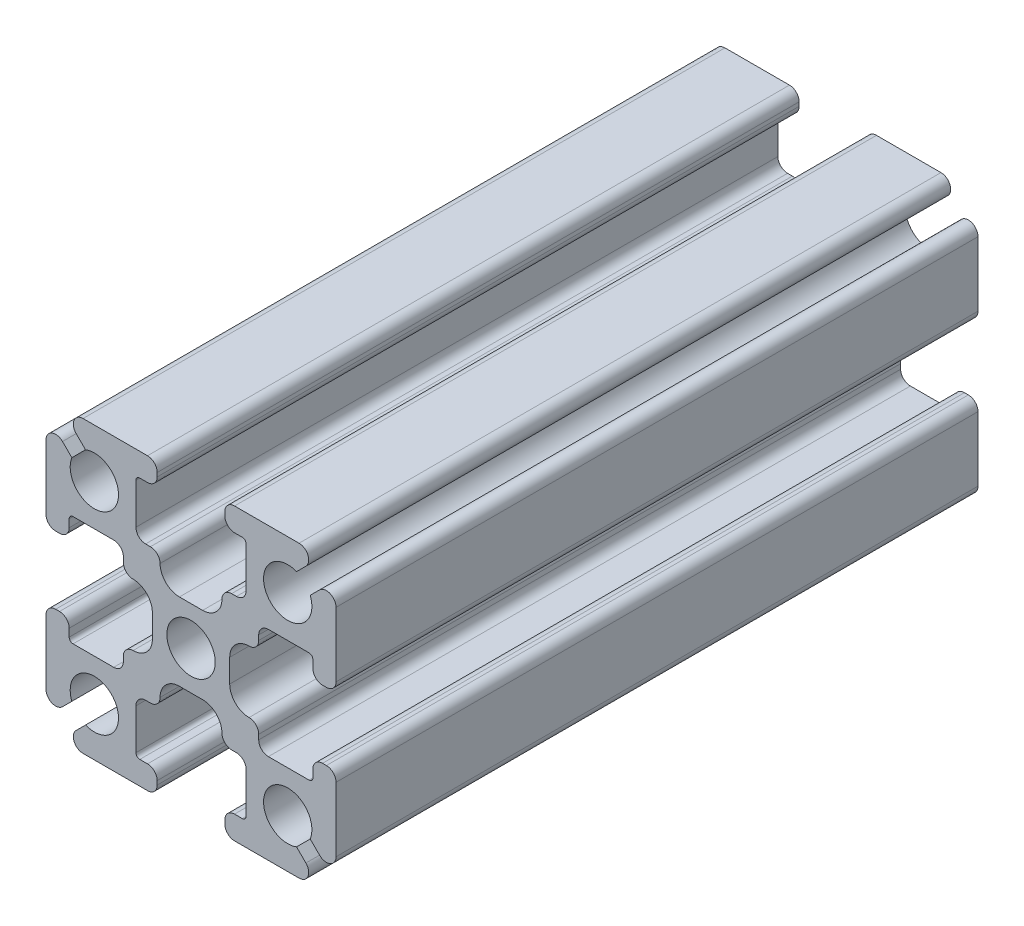
SolidWorks part; units mm, degrees
ref_plane "Front" through (0, 0, 0) normal (0, 0, 1) x (1, 0, 0)
ref_plane "Top" through (0, 0, 0) normal (0, 1, 0) x (1, 0, 0)
ref_plane "Right" through (0, 0, 0) normal (1, 0, 0) x (0, 0, -1)
sketch "Sketch1" plane through (0, 0, 0) normal (0, 0, 1) x (1, 0, 0)
  line L0 (6.6464, 5.9393) -> (6.1636, 5.4565)
  line L1 (5.4565, 6.1636) -> (5.9393, 6.6464)
  line L2 (5.5858, 7.5) -> (2.25, 7.5)
  line L3 (1.75, 7) -> (1.75, 6.8)
  line L4 (2.25, 6.3) -> (2.65, 6.3)
  line L5 (2.85, 6.1) -> (2.85, 4)
  line L6 (2.35, 3.5) -> (2.1, 3.5)
  line L7 (0.6, 2) -> (-0.6, 2)
  line L8 (-2.1, 3.5) -> (-2.35, 3.5)
  line L9 (-2.85, 4) -> (-2.85, 6.1)
  line L10 (-2.65, 6.3) -> (-2.25, 6.3)
  line L11 (-1.75, 6.8) -> (-1.75, 7)
  line L12 (-2.25, 7.5) -> (-5.5858, 7.5)
  line L13 (-5.9393, 6.6464) -> (-5.4565, 6.1636)
  line L14 (-6.1636, 5.4565) -> (-6.6464, 5.9393)
  line L15 (-7.5, 5.5858) -> (-7.5, 2.25)
  line L16 (-7, 1.75) -> (-6.8, 1.75)
  line L17 (-6.3, 2.25) -> (-6.3, 2.65)
  line L18 (-6.1, 2.85) -> (-4, 2.85)
  line L19 (-3.5, 2.35) -> (-3.5, 2.1)
  line L20 (-2, 0.6) -> (-2, -0.6)
  line L21 (-3.5, -2.1) -> (-3.5, -2.35)
  line L22 (-4, -2.85) -> (-6.1, -2.85)
  line L23 (-6.3, -2.65) -> (-6.3, -2.25)
  line L24 (-6.8, -1.75) -> (-7, -1.75)
  line L25 (-7.5, -2.25) -> (-7.5, -5.5858)
  line L26 (-6.6464, -5.9393) -> (-6.1636, -5.4565)
  line L27 (-5.4565, -6.1636) -> (-5.9393, -6.6464)
  line L28 (-5.5858, -7.5) -> (-2.25, -7.5)
  line L29 (-1.75, -7) -> (-1.75, -6.8)
  line L30 (-2.25, -6.3) -> (-2.65, -6.3)
  line L31 (-2.85, -6.1) -> (-2.85, -4)
  line L32 (-2.35, -3.5) -> (-2.1, -3.5)
  line L33 (-0.6, -2) -> (0.6, -2)
  line L34 (2.1, -3.5) -> (2.35, -3.5)
  line L35 (2.85, -4) -> (2.85, -6.1)
  line L36 (2.65, -6.3) -> (2.25, -6.3)
  line L37 (1.75, -6.8) -> (1.75, -7)
  line L38 (2.25, -7.5) -> (5.5858, -7.5)
  line L39 (5.9393, -6.6464) -> (5.4565, -6.1636)
  line L40 (6.1636, -5.4565) -> (6.6464, -5.9393)
  line L41 (7.5, -5.5858) -> (7.5, -2.25)
  line L42 (7, -1.75) -> (6.8, -1.75)
  line L43 (6.3, -2.25) -> (6.3, -2.65)
  line L44 (6.1, -2.85) -> (4, -2.85)
  line L45 (3.5, -2.35) -> (3.5, -2.1)
  line L46 (2, -0.6) -> (2, 0.6)
  line L47 (3.5, 2.1) -> (3.5, 2.35)
  line L48 (4, 2.85) -> (6.1, 2.85)
  line L49 (6.3, 2.65) -> (6.3, 2.25)
  line L50 (6.8, 1.75) -> (7, 1.75)
  line L51 (7.5, 2.25) -> (7.5, 5.5858)
  circle A0 centre (0, 0) radius 1.25
  arc A1 (6.1636, 5.4565) -> (5.4565, 6.1636) centre (5, 5) cw
  arc A2 (5.9393, 6.6464) -> (5.5858, 7.5) centre (5.5858, 7) ccw
  arc A3 (2.25, 7.5) -> (1.75, 7) centre (2.25, 7) ccw
  arc A4 (1.75, 6.8) -> (2.25, 6.3) centre (2.25, 6.8) ccw
  arc A5 (2.65, 6.3) -> (2.85, 6.1) centre (2.65, 6.1) cw
  arc A6 (2.85, 4) -> (2.35, 3.5) centre (2.35, 4) cw
  arc A7 (2.1, 3.5) -> (1.6, 3) centre (2.1, 3) ccw
  arc A8 (1.6, 3) -> (0.6, 2) centre (0.6, 3) cw
  arc A9 (-0.6, 2) -> (-1.6, 3) centre (-0.6, 3) cw
  arc A10 (-1.6, 3) -> (-2.1, 3.5) centre (-2.1, 3) ccw
  arc A11 (-2.35, 3.5) -> (-2.85, 4) centre (-2.35, 4) cw
  arc A12 (-2.85, 6.1) -> (-2.65, 6.3) centre (-2.65, 6.1) cw
  arc A13 (-2.25, 6.3) -> (-1.75, 6.8) centre (-2.25, 6.8) ccw
  arc A14 (-1.75, 7) -> (-2.25, 7.5) centre (-2.25, 7) ccw
  arc A15 (-5.5858, 7.5) -> (-5.9393, 6.6464) centre (-5.5858, 7) ccw
  arc A16 (-5.4565, 6.1636) -> (-6.1636, 5.4565) centre (-5, 5) cw
  arc A17 (-6.6464, 5.9393) -> (-7.5, 5.5858) centre (-7, 5.5858) ccw
  arc A18 (-7.5, 2.25) -> (-7, 1.75) centre (-7, 2.25) ccw
  arc A19 (-6.8, 1.75) -> (-6.3, 2.25) centre (-6.8, 2.25) ccw
  arc A20 (-6.3, 2.65) -> (-6.1, 2.85) centre (-6.1, 2.65) cw
  arc A21 (-4, 2.85) -> (-3.5, 2.35) centre (-4, 2.35) cw
  arc A22 (-3.5, 2.1) -> (-3, 1.6) centre (-3, 2.1) ccw
  arc A23 (-3, 1.6) -> (-2, 0.6) centre (-3, 0.6) cw
  arc A24 (-2, -0.6) -> (-3, -1.6) centre (-3, -0.6) cw
  arc A25 (-3, -1.6) -> (-3.5, -2.1) centre (-3, -2.1) ccw
  arc A26 (-3.5, -2.35) -> (-4, -2.85) centre (-4, -2.35) cw
  arc A27 (-6.1, -2.85) -> (-6.3, -2.65) centre (-6.1, -2.65) cw
  arc A28 (-6.3, -2.25) -> (-6.8, -1.75) centre (-6.8, -2.25) ccw
  arc A29 (-7, -1.75) -> (-7.5, -2.25) centre (-7, -2.25) ccw
  arc A30 (-7.5, -5.5858) -> (-6.6464, -5.9393) centre (-7, -5.5858) ccw
  arc A31 (-6.1636, -5.4565) -> (-5.4565, -6.1636) centre (-5, -5) cw
  arc A32 (-5.9393, -6.6464) -> (-5.5858, -7.5) centre (-5.5858, -7) ccw
  arc A33 (-2.25, -7.5) -> (-1.75, -7) centre (-2.25, -7) ccw
  arc A34 (-1.75, -6.8) -> (-2.25, -6.3) centre (-2.25, -6.8) ccw
  arc A35 (-2.65, -6.3) -> (-2.85, -6.1) centre (-2.65, -6.1) cw
  arc A36 (-2.85, -4) -> (-2.35, -3.5) centre (-2.35, -4) cw
  arc A37 (-2.1, -3.5) -> (-1.6, -3) centre (-2.1, -3) ccw
  arc A38 (-1.6, -3) -> (-0.6, -2) centre (-0.6, -3) cw
  arc A39 (0.6, -2) -> (1.6, -3) centre (0.6, -3) cw
  arc A40 (1.6, -3) -> (2.1, -3.5) centre (2.1, -3) ccw
  arc A41 (2.35, -3.5) -> (2.85, -4) centre (2.35, -4) cw
  arc A42 (2.85, -6.1) -> (2.65, -6.3) centre (2.65, -6.1) cw
  arc A43 (2.25, -6.3) -> (1.75, -6.8) centre (2.25, -6.8) ccw
  arc A44 (1.75, -7) -> (2.25, -7.5) centre (2.25, -7) ccw
  arc A45 (5.5858, -7.5) -> (5.9393, -6.6464) centre (5.5858, -7) ccw
  arc A46 (5.4565, -6.1636) -> (6.1636, -5.4565) centre (5, -5) cw
  arc A47 (6.6464, -5.9393) -> (7.5, -5.5858) centre (7, -5.5858) ccw
  arc A48 (7.5, -2.25) -> (7, -1.75) centre (7, -2.25) ccw
  arc A49 (6.8, -1.75) -> (6.3, -2.25) centre (6.8, -2.25) ccw
  arc A50 (6.3, -2.65) -> (6.1, -2.85) centre (6.1, -2.65) cw
  arc A51 (4, -2.85) -> (3.5, -2.35) centre (4, -2.35) cw
  arc A52 (3.5, -2.1) -> (3, -1.6) centre (3, -2.1) ccw
  arc A53 (3, -1.6) -> (2, -0.6) centre (3, -0.6) cw
  arc A54 (2, 0.6) -> (3, 1.6) centre (3, 0.6) cw
  arc A55 (3, 1.6) -> (3.5, 2.1) centre (3, 2.1) ccw
  arc A56 (3.5, 2.35) -> (4, 2.85) centre (4, 2.35) cw
  arc A57 (6.1, 2.85) -> (6.3, 2.65) centre (6.1, 2.65) cw
  arc A58 (6.3, 2.25) -> (6.8, 1.75) centre (6.8, 2.25) ccw
  arc A59 (7, 1.75) -> (7.5, 2.25) centre (7, 2.25) ccw
  arc A60 (7.5, 5.5858) -> (6.6464, 5.9393) centre (7, 5.5858) ccw
extrude "Boss-Extrude1" add sketch "Sketch1" along normal blind 33.1974
